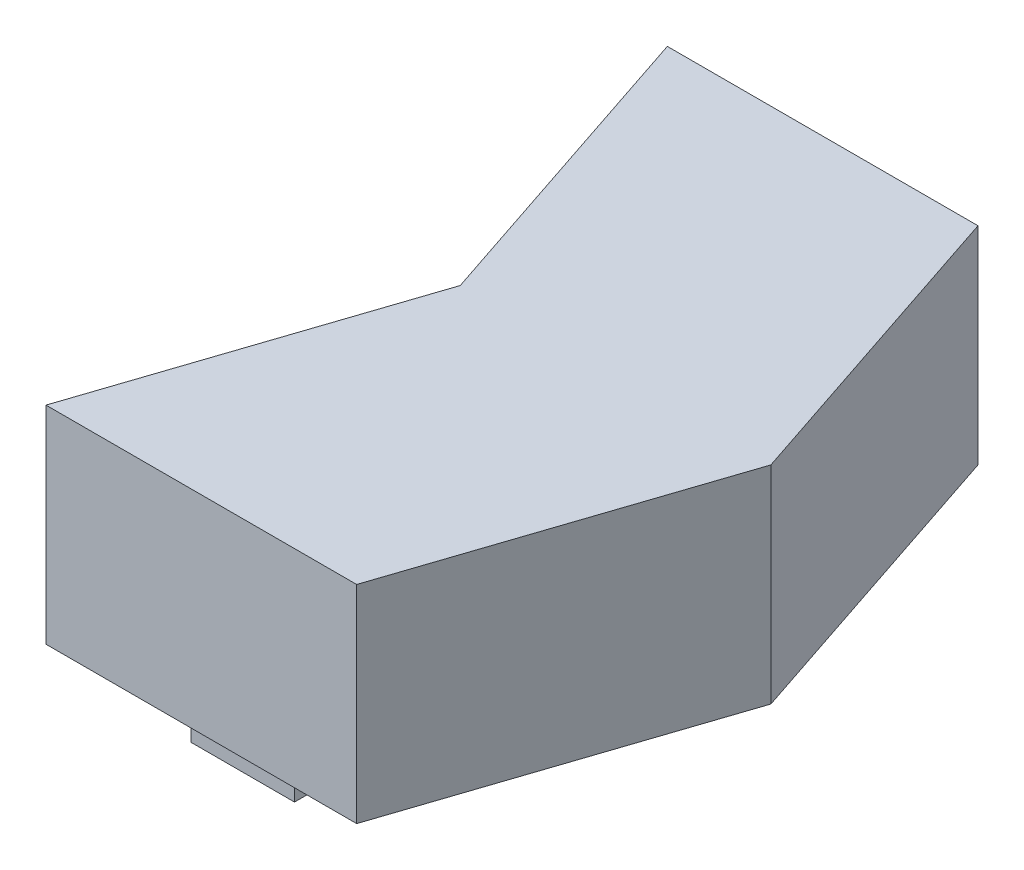
SolidWorks part; units mm, degrees
ref_plane "Front Plane" through (0, 0, 0) normal (0, 0, 1) x (1, 0, 0)
ref_plane "Top Plane" through (0, 0, 0) normal (0, 1, 0) x (1, 0, 0)
ref_plane "Right Plane" through (0, 0, 0) normal (1, 0, 0) x (0, 0, -1)
sketch "Sketch1" plane through (0, 0, 0) normal (0, 1, 0) x (1, 0, 0)
  line L0 (0, 0) -> (19.05, 0)
  line L1 (19.05, 0) -> (25.4, 19.05)
  line L2 (25.4, 19.05) -> (19.05, 38.1)
  line L3 (19.05, 38.1) -> (0, 38.1)
  line L4 (0, 38.1) -> (6.35, 19.05)
  line L5 (6.35, 19.05) -> (0, 0)
  dimension "D1" = 19.05
  dimension "D2" = 38.1
  dimension "D3" = 6.35
  dimension "D5" = 19.05
extrude "Boss-Extrude1" add sketch "Sketch1" along normal blind 12.7
sketch "Sketch2" plane through (0, 0, 0) normal (0, -1, 0) x (1, 0, 0)
  line L0 (25.4, -19.05) -> (6.35, -19.05) construction
  line L1 (6.35, -19.05) -> (0, 0) construction
  circle A0 centre (15.24, -19.05) radius 5.635
  dimension "D1" = 11.27
  dimension "D2" = 8.89
extrude "Haptic Motor Cutout" cut sketch "Sketch2" against normal blind 9.558 contours A0
sketch "Sketch3" plane through (0, 0, 0) normal (0, -1, 0) x (1, 0, 0)
  line L8 (16.51, -24.54) -> (13.97, -24.54)
  line L9 (16.51, -24.54) -> (16.51, -28.35)
  line L10 (13.97, -24.54) -> (13.97, -28.35)
  line L11 (16.51, -28.35) -> (13.97, -28.35)
  circle A3 centre (15.24, -19.05) radius 5.635 construction
  dimension "D1" = 2.54
  dimension "D2" = 3.81
extrude "Haptic Wire Cutout" cut sketch "Sketch3" against normal blind 9.558
ref_plane "MidPlane" through (0, 0, -19.05) normal (0, 0, -1) x (-1, 0, 0)
sketch "Sketch4" plane through (0, 0, 0) normal (0, -1, 0) x (1, 0, 0)
  line L0 (19.05, -38.1) -> (0, -38.1) construction
  line L1 (13.97, -36.83) -> (7.62, -36.83)
  line L2 (13.97, -36.83) -> (13.97, -34.29)
  line L3 (13.97, -34.29) -> (7.62, -34.29)
  line L4 (7.62, -36.83) -> (7.62, -34.29)
  line L5 (0, -6.985) -> (0, 6.985) construction
  dimension "D1" = 2.54
  dimension "D2" = 6.35
  dimension "D3" = 1.27
  dimension "D4" = 7.62
extrude "Pins" add sketch "Sketch4" along normal blind 2.032
mirror "Mirror1" about plane through (0, 0, -19.05) normal (0, 0, -1) of "Pins"
ref_point "Point1"
ref_axis "Axis1" through (0, 12.7, -38.1) along (0, 0, 1)
sketch "Sketch5" plane through (0, 12.7, 0) normal (0, 1, 0) x (1, 0, 0)
  line L0 (0, 38.1) -> (0, 0) construction
  line L1 (0, 19.05) -> (25.4, 19.05) construction
equation "\"Arrow Height\"= 1.5in"
equation "\"Button Height\"= 2in"
equation "\"Button Width\"= 4in"
equation "\"Haptic Diameter\"= 10mm"
equation "\"Haptic Thickness\"= 2.7mm"
equation "\"D2@Sketch1\"=\"Arrow Height\""
equation "\"D5@Sketch1\"=\"Arrow Height\"/2"
equation "\"D1@Sketch2\"=\"Haptic Diameter\"+.05in"
equation "\"D1@Haptic Motor Cutout\"=\"Haptic Thickness\" + .02+.25"
equation "\"D1@Haptic Wire Cutout\"=\"Haptic Thickness\"+.02+.25"
equation "\"Arrow Spacing\"= 1in"
equation "\"Arrow Width\"= 01in"
equation "\"Haptic Wire Angle\"= 63.43"
equation "\"Haptic Wire Width\"= .1in"
equation "\"Haptic Wire Height\"= .15in"
